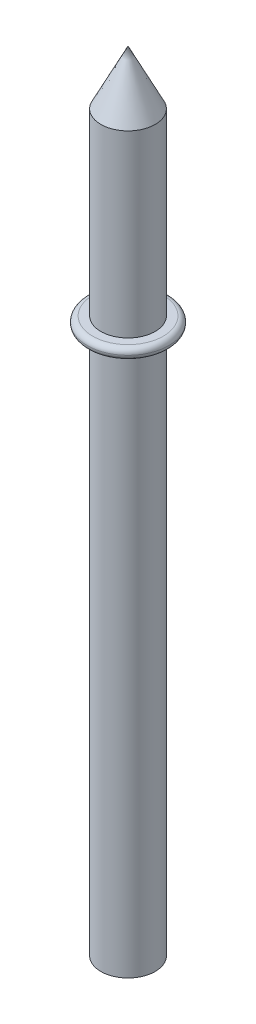
SolidWorks part; units mm, degrees
ref_plane "Front Plane" through (0, 0, 0) normal (0, 0, 1) x (1, 0, 0)
ref_plane "Top Plane" through (0, 0, 0) normal (0, 1, 0) x (1, 0, 0)
ref_plane "Right Plane" through (0, 0, 0) normal (1, 0, 0) x (0, 0, -1)
sketch "Sketch1" plane through (0, 0, 0) normal (0, 1, 0) x (1, 0, 0)
  circle A0 centre (0, 0) radius 5
  dimension "D1" = 10
extrude "Boss-Extrude1" add sketch "Sketch1" along normal blind 135
sketch "Sketch2" plane through (0, 0, 0) normal (0, 0, 1) x (1, 0, 0)
  line L0 (0, 145) -> (5, 135)
  line L1 (5, 135) -> (-5, 135) construction
  line L2 (5, 135) -> (0, 135)
  line L4 (5, 0) -> (5, 135) construction
  line L5 (0, 135) -> (0, 0) construction
  line L6 (0, 145) -> (0, 135)
  dimension "D1" = 10
revolve "Revolve3" add sketch "Sketch2" angle 360 about axis through (0, 135, 0) along (0, -1, 0)
sketch "Sketch3" plane through (0, 0, 0) normal (0, -1, 0) x (1, 0, 0)
  circle A0 centre (0, 0) radius 7.5
  circle A1 centre (0, 0) radius 5
  circle A2 centre (0, 0) radius 5 construction
  dimension "D1" = 15
extrude "Boss-Extrude2" add sketch "Sketch3" against normal blind 2 from offset 100 offset against normal yes
fillet "Fillet1" radius 1 2 edges at (0, 100, -7.5) (0, 102, -7.5)
